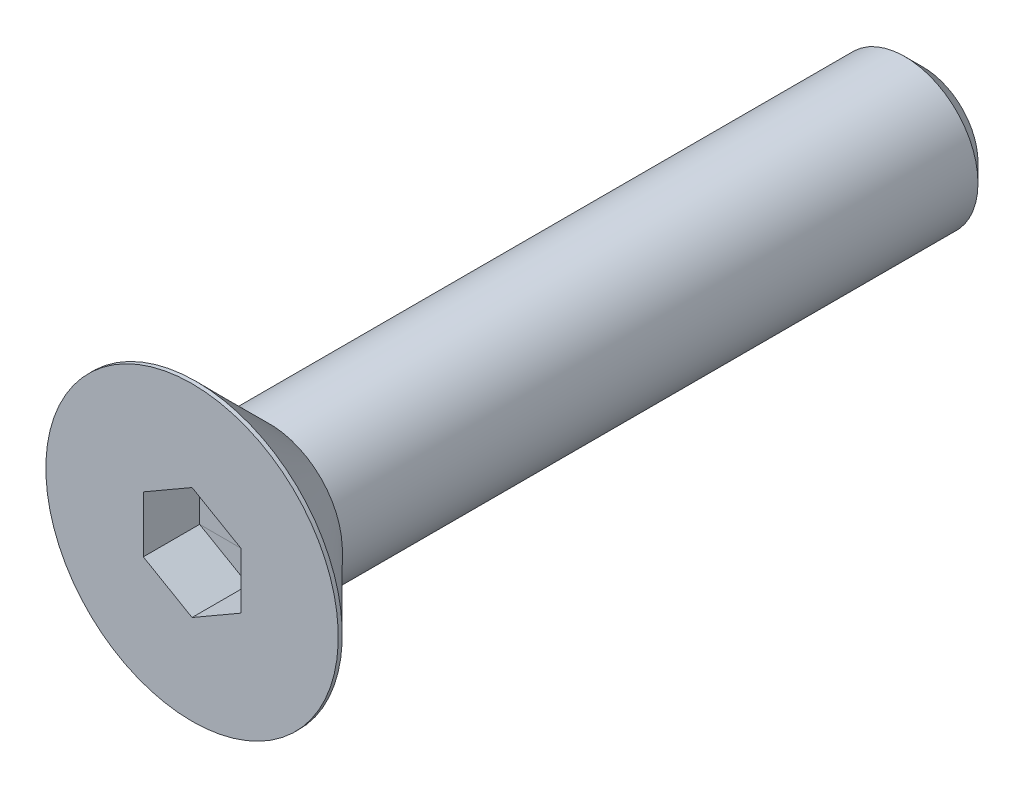
SolidWorks part; units mm, degrees
material "Chrome Stainless Steel"
ref_plane "Front" through (0, 0, 0) normal (0, 0, 1) x (1, 0, 0)
ref_plane "Top" through (0, 0, 0) normal (0, 1, 0) x (1, 0, 0)
ref_plane "Right" through (0, 0, 0) normal (1, 0, 0) x (0, 0, -1)
sketch "Sketch11" plane through (0, 0, 0) normal (1, 0, 0) x (0, 0, -1)
  line L0 (-15, 6) -> (15, 6) construction
  line L5 (-15, 6) -> (-15, -6) construction
  line L6 (15, 3) -> (15, -3) construction
  line L7 (-14.99, 2) -> (-14.99, -2) construction
  line L8 (14.9375, 3.1083) -> (15.9375, 3.1083) construction
  line L9 (15.9375, 3.1083) -> (15.4375, 2.2422) construction
  line L10 (15.4375, 2.2422) -> (14.9375, 3.1083) construction
  line L11 (15.375, 2.3505) -> (15.5, 2.3505) construction
  line L12 (15.4375, 2.3505) -> (15.4375, 2.2422) construction
  line L13 (14.9687, 3.0541) -> (15.9062, 3.0541) construction
  line L14 (15.4375, 3.1083) -> (15.4375, 3) construction
  line L15 (15, 3) -> (15.875, 3) construction
  line L17 (-14.835, 6) -> (-8.835, 0) construction
  line L18 (-8.835, 0) -> (-14.835, -6) construction
  point P3 (-11.7, 6)
  point P8 (0, 6)
  point P21 (15.4375, 3.0541)
  point P26 (-15, 0)
  point P28 (-14.99, 0)
  point P29 (15, 0)
  dimension "Length" = 30
  dimension "Head Diameter" = 12
  dimension "Thread Major Diameter" = 6
  dimension "Head Height" = 3.3
  dimension "Drive Size" = 4
  dimension "Thread Pitch" = 1
  dimension "D1" = 0.125
  dimension "D2" = 0.01
  dimension "D3" = 0.165
  dimension "Countersink Angle" = 90
sketch "Sketch1" plane through (0, 0, 0) normal (1, 0, 0) x (0, 0, -1)
  line L2 (-11.7, 3) -> (15, 3)
  line L3 (15, 3) -> (15, 0)
  line L4 (-12.69, 3) -> (-12.69, 0)
  line L5 (-11.7, 3) -> (-12.69, 3)
  line L6 (-15, 6) -> (-15, -6) construction
  line L7 (15, 3) -> (15, -3) construction
  line L8 (-12.69, 0) -> (15, 0)
  dimension "D1" = 2.31
revolve "Revolve1" add sketch "Sketch1" angle 360 mid plane about L8
chamfer "Chamfer1" distance 0.75 angle 45 1 edges at (3, 0, -15)
sketch "Sketch7" plane through (0, 0, 0) normal (1, 0, 0) x (0, 0, -1)
  line L2 (-15, 6) -> (-14.835, 6)
  line L5 (-11.7, 2.865) -> (-11.7, 0)
  line L6 (-15, 6) -> (-15, 0)
  line L8 (-15, 6) -> (-15, -6) construction
  line L9 (-15, 0) -> (-11.7, 0)
  line L12 (-14.835, 6) -> (-11.7, 2.865)
  line L13 (-14.835, 6) -> (-8.835, 0) construction
revolve "Revolve2" add sketch "Sketch7" angle 360 mid plane about L9 region at (0, 2.3546, 13.5497)
ref_plane "Plane1" through (0, 0, 11.7) normal (0, 0, 1) x (1, 0, 0)
sketch "Sketch5" plane through (0, 0, 15) normal (0, 0, 1) x (1, 0, 0)
  line L1 (2, -1.1547) -> (2, 1.1547)
  line L2 (2, 1.1547) -> (0, 2.3094)
  line L3 (0, 2.3094) -> (-2, 1.1547)
  line L4 (-2, 1.1547) -> (-2, -1.1547)
  line L5 (-2, -1.1547) -> (0, -2.3094)
  line L6 (0, -2.3094) -> (2, -1.1547)
  circle A0 centre (0, 0) radius 2 construction
extrude "Cut-Extrude2" cut sketch "Sketch5" against normal blind 2.31
sketch "Sketch6" plane through (0, 0, 15) normal (0, 0, -1) x (-1, 0, 0)
  circle A0 centre (0, 0) radius 2.3094
extrude "Cut-Extrude3" [suppressed] cut sketch "Sketch6" along normal blind 2.31 draft 45
sketch "Sketch12" [suppressed] plane through (0, 0, -15) normal (0, 0, -1) x (-1, 0, 0)
  circle A0 centre (0, 0) radius 3 construction
  circle A1 centre (0, 0) radius 3
curve "Helix/Spiral1" [suppressed] pitch 1 height 30 turns 30
sketch "Sketch13" [suppressed] plane through (0, 0, 0) normal (1, 0, 0) x (0, 0, -1)
  line L0 (14.9687, 3.0541) -> (15.9062, 3.0541)
  line L1 (15.9062, 3.0541) -> (15.5, 2.3505)
  line L2 (15.5, 2.3505) -> (15.375, 2.3505)
  line L3 (15.375, 2.3505) -> (14.9687, 3.0541)
sweep "Cut-Sweep1" [suppressed] cut profiles "Sketch13" path "Helix/Spiral1"
combine bodies "Combine1" [suppressed] operation type add bodies to combine 113 127
equation "\"D1@Chamfer1\"=\"Thread Pitch@Sketch11\" * .75"
equation "\"D1@Cut-Extrude2\"= \"Head Height@Sketch11\" * .7"
equation "\"D1@Cut-Extrude3\" = \"D1@Cut-Extrude2\""
equation "\"D1@Sketch11\"=\"Thread Pitch@Sketch11\"/8"
equation "\"D3@Sketch11\"=\"Head Height@Sketch11\"*.05"
equation "\"D4@Helix/Spiral1\"=\"Thread Pitch@Sketch11\""
equation "\"D1@Sketch1\"=\"Head Height@Sketch11\"*.7"
equation "\"D3@Helix/Spiral1\"=\"Length@Sketch11\""
